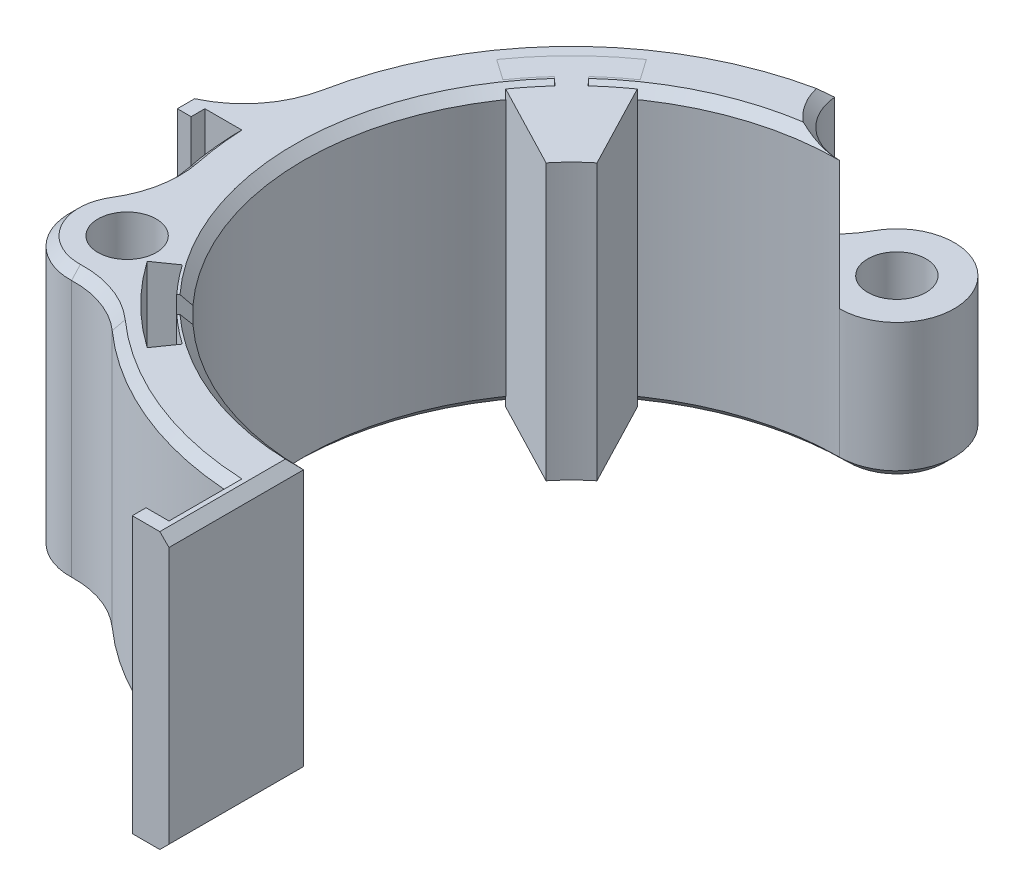
SolidWorks part; units mm, degrees
note: '?' marks a value the reader was unsure of. The reader was unsure of these and kept them because the rebuilt part matched: shared geometry of "Sketch3<6>", "Sketch4<3>".
material "PLA"
ref_plane "Front Plane" through (0, 0, 0) normal (0, 0, 1) x (1, 0, 0)
ref_plane "Top Plane" through (0, 0, 0) normal (0, 1, 0) x (1, 0, 0)
ref_plane "Right Plane" through (0, 0, 0) normal (1, 0, 0) x (0, 0, -1)
sketch "Sketch3" plane through (0, 0, 0) normal (0, 1, 0) x (1, 0, 0)
  line L0 (0, 29.195) -> (0, 35.445)
  line L1 (0, -29.195) -> (0, -35.445)
  line L3 (0, -42.3567) -> (-2.5, -42.3567)
  line L6 (-35.445, 0) -> (-38.445, 0)
  line L7 (0, -42.3567) -> (-4, -42.3567)
  line L8 (0, -42.3567) -> (0, -43.8567)
  line L9 (0, -43.8567) -> (-4, -43.8567)
  line L10 (-2.5, -42.3567) -> (0, -42.3567)
  line L11 (-4, -42.3567) -> (-4, -43.8567)
  line L12 (-38.445, 0) -> (-38.445, -1.5)
  line L13 (-38.445, -1.5) -> (-35.4132, -1.5)
  line L14 (-35.4132, -1.5) -> (-35.445, 0)
  line L15 (-2.5, -42.3567) -> (-2.5, -35.3567)
  line L16 (-38.445, 0) -> (-39.945, 0)
  line L17 (-38.445, 0) -> (-38.445, -3)
  line L18 (-38.445, -3) -> (-39.945, -3)
  line L19 (-39.945, 0) -> (-39.945, -3)
  line L20 (-2.5, -29.0877) -> (0, -29.195)
  line L21 (0, -42.3567) -> (0, -29.195)
  line L22 (0, 0) -> (0, 50000) construction
  arc A0 (0, -29.195) -> (0, 29.195) centre (0, 0) cw
  arc A1 (0, -35.445) -> (0, 35.445) centre (0, 0) cw
  circle A2 centre (0, 35.445) radius 3.175
  circle A3 centre (0, 35.445) radius 6.25
  circle A4 centre (30.6962, -17.7225) radius 3.175
  circle A5 centre (30.6962, -17.7225) radius 6.25
  circle A6 centre (-30.6962, -17.7225) radius 3.175
  circle A7 centre (-30.6962, -17.7225) radius 6.25
  point P33 (0, 0)
  dimension "D1" = 29.195
  dimension "D5" = 12.5
  dimension "D6" = 6.35
  dimension "D4" = 2.5
  dimension "D7" = 1.5
  dimension "D8" = 4
  dimension "D9" = 1.5
  dimension "D10" = 3
  dimension "D11" = 3
  dimension "D12" = 1.5
  dimension "D3" = 7
  dimension "D13" = 3
extrude "Boss-Extrude2" add sketch "Sketch3" along normal blind 30 contours A7 A0 A3 A1 L14 | A1 A7 A6 | A1 A7 A6 | A1 A6 | A7 A1 L1 A0 | L21 A1 L15 L3 | L7 L11 L9 L8 L3 | L17 L16 L19 L18
extrude "Boss-Extrude3" add sketch "Sketch3<6>" along normal offset from surface (15 mm away) 15 contours L0 A3 A1 A2 | A1 A3 L0 A2 | L22 A2 L0 A3
sketch "Sketch3<6>" plane through (0, 0, 0) normal (0, 1, 0) x (1, 0, 0) same geometry as "Sketch3"
fillet "Fillet1" radius 10 4 edges at (-27.1062, 15, 22.8386) (-33.3319, 15, 12.0554) (-6.2257, 7.5, -34.8939) (-35.445, 15, 0)
chamfer "Chamfer1" distance 1 angle 45 23 edges at (-2.5, 0, 38.8567) (-2.5, 30, 38.8567) (-13.7584, 0, 32.6658) (-13.7584, 30, 32.6658) (-26.7845, 30, 24.5637) (-26.7845, 0, 24.5637) (-36.1089, 0, 20.8475) (-36.1089, 30, 20.8475) (-35.1785, 0, 4.3385) (-35.1785, 30, 4.3385) (-34.665, 30, 10.9142) (-34.665, 0, 10.9142) (-36.5692, 30, -2.8688) (-36.5692, 0, -2.8688) (-26.5703, 0, -23.4599) (-7.8805, 0, -35.4779) (5.3637, 0, -38.6533) (0, 0, 36.5258) (0, 30, 36.5258) (-29.195, 0, 0) (-24.8143, 30, -25.31) (-4.2201, 30, -30.8349) (-29.195, 30, 0)
sketch "Sketch4" plane through (0, 30, 0) normal (0, 1, 0) x (1, 0, 0)
  line L0 (0.4951, -0.3466) -> (-32997.8309, 23105.33) construction
  line L1 (0, 0) -> (-23105.6766, 32998.326) construction
  line L2 (-27.1917, 19.0399) -> (-24.9391, 17.4625)
  line L3 (-19.0399, 27.1917) -> (-17.4625, 24.9391)
  line L4 (-22.4464, 20.5683) -> (-21.5248, 19.7238)
  line L5 (-20.5683, 22.4464) -> (-19.7238, 21.5248)
  line L6 (-21.5248, 19.7238) -> (0, 0) construction
  line L7 (0, 0) -> (-19.7238, 21.5248) construction
  line L8 (-23.9151, 16.7456) -> (-14.7512, 11.9751)
  line L9 (-16.7456, 23.9151) -> (-11.9751, 14.7512)
  line L10 (-21.5278, 21.5278) -> (0, 0) construction
  line L11 (0, -200000) -> (0, 250000) construction
  arc A0 (-19.0399, 27.1917) -> (-27.1917, 19.0399) centre (0, 0) ccw
  arc A1 (-17.4625, 24.9391) -> (-24.9391, 17.4625) centre (0, 0) ccw
  arc A2 (-7.0412, 33.7176) -> (-33.7832, 6.7194) centre (0, 0) ccw construction
  arc A4 (0, 29.195) -> (0, -29.195) centre (0, 0) ccw construction
  arc A5 (-21.5248, 19.7238) -> (-23.9151, 16.7456) centre (0, 0) ccw
  arc A6 (-19.7238, 21.5248) -> (-16.7456, 23.9151) centre (0, 0) cw
  arc A7 (-11.9751, 14.7512) -> (-14.7512, 11.9751) centre (0, 0) ccw
  point P23 (-16.861, 25.3496)
  point P25 (-18.1332, 24.4558)
  arc M18 (-1, -30.1784) -> (-4.6014, 29.8423) centre (0, 0) cw
  dimension "D2" = 1.25
  dimension "D3" = 1.25
  dimension "D8" = 19
  dimension "D1" = 45
  dimension "D4" = 5
  dimension "D5" = 7.5
  dimension "D6" = 7.5
  dimension "D7" = 7.5
  dimension "D9" = 7.5
extrude "jaw_slot" cut sketch "Sketch4" against normal through all both and the other way through all contours A1 L3 A0 L2 | A7 L9 A6 L5 L4 A5 L8 M18 | L5 A1 L4 M18
extrude "tpu_jaw" add sketch "Sketch4<3>" against normal up to surface (30 mm away) separate body contours A1 L3 A0 L2 | A7 L9 A6 L5 L4 A5 L8 M18 | L5 A1 L4 M18 up to face at (0, 0, -32.27)
sketch "Sketch4<3>" plane through (0, 30, 0) normal (0, 1, 0) x (1, 0, 0) same geometry as "Sketch4"
ref_axis "Axis1" through (0, -1.5249, 0) along (0, 1, 0)?
pattern_circular "slot_pattern" count 2 every 90 about axis through (0, -1.5249, 0) along (0, 1, 0) of "jaw_slot"
equation "\"Diameter\"= 2.298817in'Diameter of the outer surface of the body tube."
equation "\"Radius\"= \"Diameter\" / 2"
equation "\"D1@Sketch3\"=\"Radius\""
